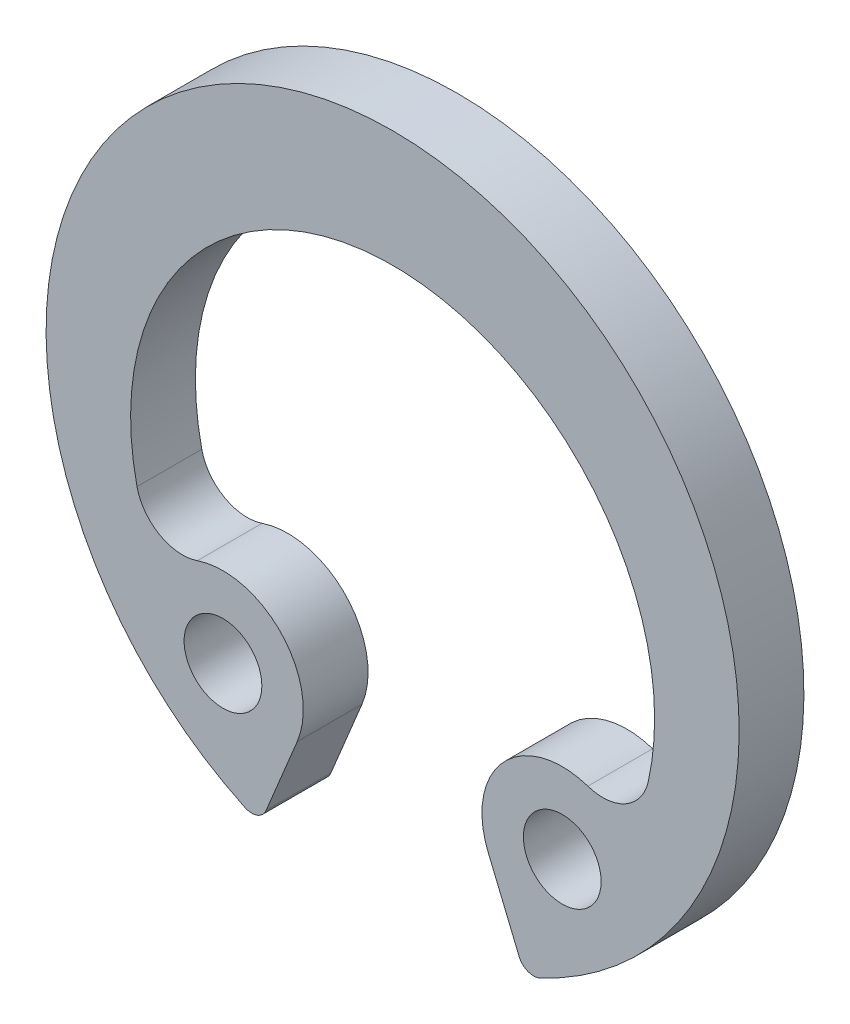
SolidWorks part; units mm, degrees
ref_plane "Front Plane" through (0, 0, 0) normal (0, 0, 1) x (1, 0, 0)
ref_plane "Top Plane" through (0, 0, 0) normal (0, 1, 0) x (1, 0, 0)
ref_plane "Right Plane" through (0, 0, 0) normal (1, 0, 0) x (0, 0, -1)
sketch "BodySke" plane through (0, 0, 0) normal (0, 0, 1) x (1, 0, 0)
  line L0 (0, -7.6074) -> (0, 7.215) construction
  line L1 (1.4734, -3.5572) -> (2.0474, -4.9428)
  line L2 (-1.4734, -3.5572) -> (-2.0474, -4.9428)
  line L3 (2.0474, -4.9428) -> (5.9992, -4.9428) construction
  line L4 (3.0935, -1.9371) -> (3.6777, -2.1791)
  line L5 (-3.0935, -1.9371) -> (-3.6777, -2.1791)
  arc A0 (2.0474, -4.9428) -> (-2.0474, -4.9428) centre (0, 0) ccw
  arc A1 (0, -4.54) -> (3.6046, -2.3304) centre (0, -0.495) ccw construction
  circle A2 centre (2.619, -3.0827) radius 0.6
  circle A3 centre (0, 0) radius 4.045 construction
  circle A4 centre (-2.619, -3.0827) radius 0.6
  arc A5 (-3.6777, -2.1791) -> (3.6777, -2.1791) centre (0, -0.495) cw
  arc A6 (3.6046, -2.3304) -> (3.4297, -2.1445) centre (2.619, -3.0827) ccw construction
  arc A8 (3.0935, -1.9371) -> (1.4734, -3.5572) centre (2.619, -3.0827) ccw
  arc A9 (3.6777, -2.1791) -> (-3.6777, -2.1791) centre (0, -0.495) ccw
  arc A10 (-3.0935, -1.9371) -> (-1.4734, -3.5572) centre (-2.619, -3.0827) cw
  dimension "D3" = 8.09
  dimension "Hole_dia" = 1.2
  dimension "Groove_length" = 3.1
  dimension "D2" = 22.5
  dimension "D1" = 45
extrude "BaseBody" add sketch "BodySke" along normal blind 1 contours A1 L1 A0 | A1 | A1 | A9 L2 A4 region at (1.8472, -2.3109, 0)
fillet "Fillet1" radius 0.72 2 edges at (3.6777, -2.1791, 0.5) (-3.6777, -2.1791, 0.5)
fillet "Fillet2" radius 0.24 2 edges at (2.0474, -4.9428, 0.5) (-2.0474, -4.9428, 0.5)
equation "\"D3@BodySke\" = \"Groove_Diameter@BodySke\" - 1.45 * \"Groove_depth@BodySke\""
equation "\"D1@Fillet1\" = \"Hole_dia@BodySke\" * 0.6"
equation "\"D1@Fillet2\" = \"Hole_dia@BodySke\" * 0.2"
